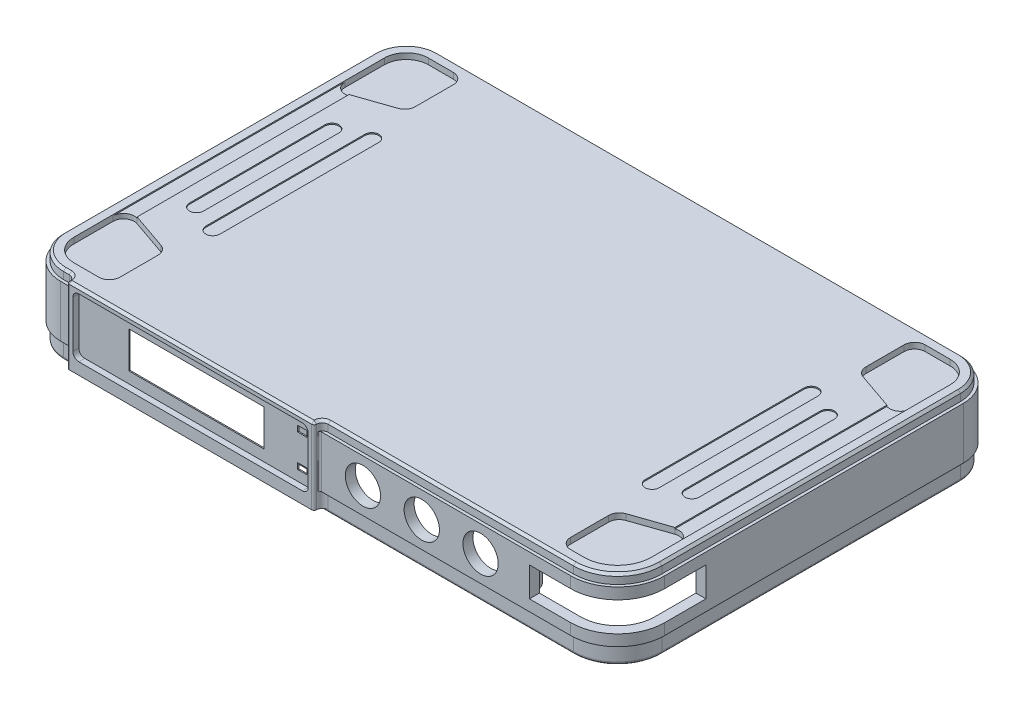
SolidWorks part; units mm, degrees
ref_plane "Front Plane" through (0, 0, 0) normal (0, 0, 1) x (1, 0, 0)
ref_plane "Top Plane" through (0, 0, 0) normal (0, 1, 0) x (1, 0, 0)
ref_plane "Right Plane" through (0, 0, 0) normal (1, 0, 0) x (0, 0, -1)
sketch "Sketch1" plane through (0, 0, 0) normal (0, 1, 0) x (1, 0, 0)
  line L0 (-50.35, 0) -> (50.35, 0) construction
  line L1 (0, 32.39) -> (0, -32.39) construction
  line L8 (44.35, 32.39) -> (-44.35, 32.39)
  line L9 (-50.35, 26.39) -> (-50.35, -26.39)
  line L10 (-44.35, -32.39) -> (42.35, -32.39)
  line L11 (50.35, -24.39) -> (50.35, 26.39)
  arc A2 (42.35, -32.39) -> (50.35, -24.39) centre (42.35, -24.39) ccw
  arc A8 (50.35, 26.39) -> (44.35, 32.39) centre (44.35, 26.39) ccw
  arc A9 (-44.35, 32.39) -> (-50.35, 26.39) centre (-44.35, 26.39) ccw
  arc A10 (-50.35, -26.39) -> (-44.35, -32.39) centre (-44.35, -26.39) ccw
  dimension "D2" = 64.78
  dimension "D3" = 6
  dimension "D1" = 100.7
  dimension "D4" = 0
  dimension "D5" = 8
extrude "Boss-Extrude1" add sketch "Sketch1" along normal blind 13
sketch "Sketch3" plane through (0, 13, 0) normal (0, 1, 0) x (1, 0, 0)
  line L0 (-50.35, 0) -> (50.35, 0) construction
  line L1 (-50.35, 26.39) -> (-50.35, -26.39) construction
  line L2 (42.35, -30.1389) -> (40.0989, -30.1389)
  line L3 (0, -32.39) -> (0, 32.39) construction
  line L4 (-44.35, -32.39) -> (42.35, -32.39) construction
  line L5 (50.35, -24.39) -> (50.35, 26.39) construction
  line L6 (-45.9859, -18.557) -> (-39.9859, -20.6263) construction
  line L8 (-48.0989, -19.7157) -> (-48.0989, -26.39)
  line L9 (-39.5121, -20.1524) -> (-45.7121, -18.014)
  line L10 (-38.2989, -28.3389) -> (-38.2989, -21.854)
  line L11 (-44.35, -30.1389) -> (-40.0989, -30.1389)
  line L13 (44.35, 32.39) -> (-44.35, 32.39) construction
  line L14 (-44.35, 30.1389) -> (-40.0989, 30.1389)
  line L15 (-38.2989, 28.3389) -> (-38.2989, 21.854)
  line L16 (-39.5121, 20.1524) -> (-45.7121, 18.014)
  line L17 (-48.0989, 19.7157) -> (-48.0989, 26.39)
  line L18 (48.0989, 19.7157) -> (48.0989, 26.39)
  line L19 (39.5121, 20.1524) -> (45.7121, 18.014)
  line L20 (38.2989, 28.3389) -> (38.2989, 21.854)
  line L21 (44.35, 30.1389) -> (40.0989, 30.1389)
  line L23 (38.2989, -28.3389) -> (38.2989, -21.854)
  line L24 (39.5121, -20.1524) -> (45.7121, -18.014)
  line L25 (48.0989, -19.7157) -> (48.0989, -24.39)
  arc A0 (-40.0989, 30.1389) -> (-38.2989, 28.3389) centre (-40.0989, 28.3389) cw
  arc A1 (-38.2989, 21.854) -> (-39.5121, 20.1524) centre (-40.0989, 21.854) cw
  arc A2 (-45.7121, 18.014) -> (-48.0989, 19.7157) centre (-46.2989, 19.7157) cw
  arc A3 (-48.0989, 26.39) -> (-44.35, 30.1389) centre (-44.35, 26.39) cw
  arc A4 (-50.35, -26.39) -> (-44.35, -32.39) centre (-44.35, -26.39) ccw construction
  arc A5 (42.35, -32.39) -> (50.35, -24.39) centre (42.35, -24.39) ccw construction
  arc A6 (38.2989, -28.3389) -> (40.0989, -30.1389) centre (40.0989, -28.3389) ccw
  arc A8 (-48.0989, -26.39) -> (-44.35, -30.1389) centre (-44.35, -26.39) ccw
  arc A9 (-45.7121, -18.014) -> (-48.0989, -19.7157) centre (-46.2989, -19.7157) ccw
  arc A10 (-38.2989, -21.854) -> (-39.5121, -20.1524) centre (-40.0989, -21.854) ccw
  arc A11 (-40.0989, -30.1389) -> (-38.2989, -28.3389) centre (-40.0989, -28.3389) ccw
  arc A13 (38.2989, -21.854) -> (39.5121, -20.1524) centre (40.0989, -21.854) cw
  arc A14 (45.7121, -18.014) -> (48.0989, -19.7157) centre (46.2989, -19.7157) cw
  arc A15 (48.0989, -24.39) -> (42.35, -30.1389) centre (42.35, -24.39) cw
  arc A16 (48.0989, 26.39) -> (44.35, 30.1389) centre (44.35, 26.39) ccw
  arc A17 (45.7121, 18.014) -> (48.0989, 19.7157) centre (46.2989, 19.7157) ccw
  arc A18 (38.2989, 21.854) -> (39.5121, 20.1524) centre (40.0989, 21.854) ccw
  arc A19 (40.0989, 30.1389) -> (38.2989, 28.3389) centre (40.0989, 28.3389) ccw
  point P64 (-38.8262, -29.6117)
  point P65 (-47.3438, -18.25)
  point P66 (-38.6333, -20.8091)
  point P67 (-47.0009, -29.0409)
  point P68 (-38.6333, 20.8091)
  point P75 (-47.3438, 18.25)
  dimension "D3" = 36.5
  dimension "D1" = 1.8
  dimension "D6" = 0
  dimension "D7" = 0
  dimension "D2" = 9.8
  dimension "D5" = 14.2
  dimension "D9" = 4.2511
extrude "Cut-Extrude1" cut sketch "Sketch3" against normal blind 1 contours L11 A11 L10 A10 L9 A9 L8 A8 | A15 L25 A14 L24 A13 L23 A6 L2 | L21 A19 L20 A18 L19 A17 L18 A16 | A3 L17 A2 L16 A1 L15 A0 L14
sketch "Sketch4" plane through (0, 13, 0) normal (0, 1, 0) x (1, 0, 0)
  line L0 (-48.0989, 19.7157) -> (-48.0989, -19.7157)
  line L1 (-45.7121, 0) -> (-48.0989, 0) construction
  line L2 (-40.9252, 0) -> (-43.3121, 0) construction
  line L3 (-42.1186, 11.5066) -> (-42.1186, -11.5066) construction
  line L4 (-40.9252, 11.5066) -> (-40.9252, -11.5066)
  line L5 (-45.7121, 18.014) -> (-45.7121, -18.014)
  line L6 (-43.3121, 11.5066) -> (-43.3121, -11.5066)
  line L7 (-37.3317, 13.5066) -> (-37.3317, -13.5066) construction
  line L8 (-36.1383, 13.5066) -> (-36.1383, -13.5066)
  line L9 (-38.5252, 13.5066) -> (-38.5252, -13.5066)
  line L10 (-36.1383, 0) -> (-38.5252, 0) construction
  line L11 (-45.7121, 0) -> (-43.3121, 0) construction
  line L12 (-40.9252, 0) -> (-38.5252, 0) construction
  line L13 (0, 32.39) -> (0, -32.39) construction
  line L14 (44.35, 32.39) -> (-44.35, 32.39) construction
  line L16 (42.1186, 11.5066) -> (42.1186, -11.5066) construction
  line L17 (40.9252, 11.5066) -> (40.9252, -11.5066)
  line L18 (43.3121, 11.5066) -> (43.3121, -11.5066)
  line L19 (37.3317, 13.5066) -> (37.3317, -13.5066) construction
  line L20 (36.1383, 13.5066) -> (36.1383, -13.5066)
  line L21 (38.5252, 13.5066) -> (38.5252, -13.5066)
  line L22 (40.9252, 0) -> (38.5252, 0) construction
  line L23 (45.7121, 0) -> (43.3121, 0) construction
  line L24 (36.1383, 0) -> (38.5252, 0) construction
  line L25 (40.9252, 0) -> (43.3121, 0) construction
  line L26 (45.7121, 0) -> (48.0989, 0) construction
  line L27 (45.7121, 18.014) -> (45.7121, -18.014)
  line L28 (48.0989, 19.7157) -> (48.0989, -19.7157)
  arc A0 (-48.0989, 19.7157) -> (-45.7121, 18.014) centre (-46.2989, 19.7157) ccw construction
  arc A1 (-45.7121, -18.014) -> (-48.0989, -19.7157) centre (-46.2989, -19.7157) ccw construction
  arc A2 (-48.0989, 19.7157) -> (-45.7121, 18.014) centre (-46.2989, 19.7157) ccw
  arc A3 (-45.7121, -18.014) -> (-48.0989, -19.7157) centre (-46.2989, -19.7157) ccw
  arc A4 (-40.9252, 11.5066) -> (-43.3121, 11.5066) centre (-42.1186, 11.5066) ccw
  arc A5 (-43.3121, -11.5066) -> (-40.9252, -11.5066) centre (-42.1186, -11.5066) ccw
  arc A6 (-36.1383, 13.5066) -> (-38.5252, 13.5066) centre (-37.3317, 13.5066) ccw
  arc A7 (-38.5252, -13.5066) -> (-36.1383, -13.5066) centre (-37.3317, -13.5066) ccw
  arc A8 (40.9252, 11.5066) -> (43.3121, 11.5066) centre (42.1186, 11.5066) cw
  arc A9 (43.3121, -11.5066) -> (40.9252, -11.5066) centre (42.1186, -11.5066) cw
  arc A10 (36.1383, 13.5066) -> (38.5252, 13.5066) centre (37.3317, 13.5066) cw
  arc A11 (38.5252, -13.5066) -> (36.1383, -13.5066) centre (37.3317, -13.5066) cw
  arc A12 (45.7121, -18.014) -> (48.0989, -19.7157) centre (46.2989, -19.7157) cw
  arc A13 (48.0989, 19.7157) -> (45.7121, 18.014) centre (46.2989, 19.7157) cw
  point P4 (-42.1186, 0)
  point P10 (-42.1186, 12.7)
  point P11 (-42.1186, -12.7)
  point P17 (-37.3317, 0)
  point P28 (-37.3317, -14.7)
  point P29 (-37.3317, 14.7)
  point P38 (42.1186, 0)
  point P45 (37.3317, 0)
  point P62 (37.3317, 14.7)
  point P63 (37.3317, -14.7)
  point P64 (42.1186, -12.7)
  point P65 (42.1186, 12.7)
  dimension "D1" = 8.0188
  dimension "D2" = 2.4
  dimension "D3" = 25.4
  dimension "D4" = 29.4
extrude "Cut-Extrude2" cut sketch "Sketch4" against normal blind 0.2
sketch "Sketch5" plane through (0, 13, 0) normal (0, 1, 0) x (1, 0, 0)
  line L0 (44.35, 31.89) -> (-44.35, 31.89)
  line L1 (-49.85, 26.39) -> (-49.85, -26.39)
  line L2 (-44.35, -31.89) -> (42.35, -31.89)
  line L3 (49.85, -24.39) -> (49.85, 26.39)
  line L4 (44.35, 32.39) -> (-44.35, 32.39)
  line L5 (-50.35, 26.39) -> (-50.35, -26.39)
  line L6 (-44.35, -32.39) -> (42.35, -32.39)
  line L7 (50.35, -24.39) -> (50.35, 26.39)
  line L8 (44.35, 32.39) -> (-44.35, 32.39)
  line L9 (-50.35, 26.39) -> (-50.35, -26.39)
  line L10 (-44.35, -32.39) -> (42.35, -32.39)
  line L11 (50.35, -24.39) -> (50.35, 26.39)
  arc A0 (-44.35, 31.89) -> (-49.85, 26.39) centre (-44.35, 26.39) ccw
  arc A1 (-49.85, -26.39) -> (-44.35, -31.89) centre (-44.35, -26.39) ccw
  arc A2 (42.35, -31.89) -> (49.85, -24.39) centre (42.35, -24.39) ccw
  arc A3 (49.85, 26.39) -> (44.35, 31.89) centre (44.35, 26.39) ccw
  arc A4 (50.35, 26.39) -> (44.35, 32.39) centre (44.35, 26.39) ccw
  arc A5 (-44.35, 32.39) -> (-50.35, 26.39) centre (-44.35, 26.39) ccw
  arc A6 (-50.35, -26.39) -> (-44.35, -32.39) centre (-44.35, -26.39) ccw
  arc A7 (42.35, -32.39) -> (50.35, -24.39) centre (42.35, -24.39) ccw
  arc A8 (50.35, 26.39) -> (44.35, 32.39) centre (44.35, 26.39) ccw
  arc A9 (-44.35, 32.39) -> (-50.35, 26.39) centre (-44.35, 26.39) ccw
  arc A10 (-50.35, -26.39) -> (-44.35, -32.39) centre (-44.35, -26.39) ccw
  arc A11 (42.35, -32.39) -> (50.35, -24.39) centre (42.35, -24.39) ccw
  dimension "D2" = 0.5
  dimension "D1" = 0
extrude "Cut-Extrude3" cut sketch "Sketch5" against normal blind 1.6
sketch "Sketch6" plane through (0, 0, 0) normal (0, -1, 0) x (1, 0, 0)
  line L4 (-44.35, -32.39) -> (44.35, -32.39)
  line L5 (-50.35, 26.39) -> (-50.35, -26.39)
  line L6 (42.35, 32.39) -> (-44.35, 32.39)
  line L7 (50.35, -26.39) -> (50.35, 24.39)
  line L8 (-44.35, -32.39) -> (44.35, -32.39)
  line L9 (-50.35, 26.39) -> (-50.35, -26.39)
  line L10 (42.35, 32.39) -> (-44.35, 32.39)
  line L11 (50.35, -26.39) -> (50.35, 24.39)
  line L12 (49.85, -26.39) -> (49.85, 24.39)
  line L13 (-44.35, -31.89) -> (44.35, -31.89)
  line L14 (-49.85, 26.39) -> (-49.85, -26.39)
  line L15 (42.35, 31.89) -> (-44.35, 31.89)
  line L16 (49.85, -26.39) -> (49.85, 24.39)
  line L17 (-44.35, -31.89) -> (44.35, -31.89)
  line L18 (-49.85, 26.39) -> (-49.85, -26.39)
  line L19 (42.35, 31.89) -> (-44.35, 31.89)
  arc A4 (44.35, -32.39) -> (50.35, -26.39) centre (44.35, -26.39) ccw
  arc A5 (-50.35, -26.39) -> (-44.35, -32.39) centre (-44.35, -26.39) ccw
  arc A6 (-44.35, 32.39) -> (-50.35, 26.39) centre (-44.35, 26.39) ccw
  arc A7 (50.35, 24.39) -> (42.35, 32.39) centre (42.35, 24.39) ccw
  arc A8 (44.35, -32.39) -> (50.35, -26.39) centre (44.35, -26.39) ccw
  arc A9 (-50.35, -26.39) -> (-44.35, -32.39) centre (-44.35, -26.39) ccw
  arc A10 (-44.35, 32.39) -> (-50.35, 26.39) centre (-44.35, 26.39) ccw
  arc A11 (50.35, 24.39) -> (42.35, 32.39) centre (42.35, 24.39) ccw
  arc A12 (44.35, -31.89) -> (49.85, -26.39) centre (44.35, -26.39) ccw
  arc A13 (-49.85, -26.39) -> (-44.35, -31.89) centre (-44.35, -26.39) ccw
  arc A14 (-44.35, 31.89) -> (-49.85, 26.39) centre (-44.35, 26.39) ccw
  arc A15 (49.85, 24.39) -> (42.35, 31.89) centre (42.35, 24.39) ccw
  arc A16 (44.35, -31.89) -> (49.85, -26.39) centre (44.35, -26.39) ccw
  arc A17 (-49.85, -26.39) -> (-44.35, -31.89) centre (-44.35, -26.39) ccw
  arc A18 (-44.35, 31.89) -> (-49.85, 26.39) centre (-44.35, 26.39) ccw
  arc A19 (49.85, 24.39) -> (42.35, 31.89) centre (42.35, 24.39) ccw
  dimension "D1" = 0
  dimension "D2" = 0
extrude "Cut-Extrude4" cut sketch "Sketch6" against normal blind 2.6
sketch "Sketch7" plane through (0, 0, 31.89) normal (0, 0, 1) x (1, 0, 0)
  line L0 (-44.35, 13) -> (42.35, 13) construction
  line L1 (-42.35, 13) -> (-0.35, 13)
  line L2 (-42.35, 13) -> (-42.35, 0)
  line L3 (-42.35, 0) -> (-0.35, 0)
  line L4 (-0.35, 13) -> (-0.35, 0)
  line L5 (-42.35, 13) -> (-0.35, 0) construction
  line L6 (-42.35, 0) -> (-0.35, 13) construction
  line L7 (42.35, 0) -> (-44.35, 0) construction
  line L8 (-50.35, 11.4) -> (-50.35, 2.6) construction
  point P0 (-21.35, 6.5)
  dimension "D1" = 42
  dimension "D2" = 8
extrude "Boss-Extrude2" add sketch "Sketch7" along normal blind 1.4
sketch "Sketch8" plane through (-49.85, 0, 0) normal (-1, 0, 0) x (0, 0, 1)
  line L0 (0, 0) -> (0, 13) construction
  line L1 (26.39, 0) -> (-26.39, 0) construction
  line L2 (-26.39, 13) -> (26.39, 13) construction
  line L3 (-32.39, 11.4) -> (-32.39, 2.6) construction
  line L4 (-13.39, 11.4) -> (-13.39, 2.6) construction
  line L5 (-26.39, 11.4) -> (26.39, 11.4) construction
  line L6 (26.39, 2.6) -> (-26.39, 2.6) construction
  circle A0 centre (-13.39, 7) radius 6
  circle A1 centre (13.39, 7) radius 6
  point P8 (-19.39, 7)
  point P13 (-7.39, 6.5)
  point P16 (7.39, 6.5)
  point P17 (19.39, 7)
  line M5 (-26.39, 11.4) -> (26.39, 11.4)
  dimension "D1" = 12
  dimension "D2" = 13
extrude "Cut-Extrude6" cut sketch "Sketch8" along normal up to surface (0.5 mm away) contours A0 M5 | A1 M5 up to face at (-50.35, 7, 0)
sketch "Sketch9" plane through (0, 0, 33.29) normal (0, 0, 1) x (1, 0, 0)
  line L0 (-42.35, 0) -> (-0.35, 0) construction
  line L1 (-40.35, 12) -> (-2.35, 12)
  line L2 (-41.35, 11) -> (-41.35, 3)
  line L3 (-40.35, 2) -> (-2.35, 2)
  line L4 (-1.35, 11) -> (-1.35, 3)
  line L5 (-41.35, 12) -> (-1.35, 2) construction
  line L6 (-41.35, 2) -> (-1.35, 12) construction
  line L7 (-42.35, 7) -> (-0.35, 7) construction
  line L8 (-42.35, 11.4) -> (-42.35, 2.6) construction
  line L9 (-0.35, 2.6) -> (-0.35, 11.4) construction
  line L10 (-21.35, 13) -> (-21.35, 0) construction
  line L11 (-0.35, 13) -> (-42.35, 13) construction
  arc A0 (-40.35, 12) -> (-41.35, 11) centre (-40.35, 11) ccw
  arc A1 (-41.35, 3) -> (-40.35, 2) centre (-40.35, 3) ccw
  arc A2 (-1.35, 3) -> (-2.35, 2) centre (-2.35, 3) cw
  arc A3 (-2.35, 12) -> (-1.35, 11) centre (-2.35, 11) cw
  point P0 (-21.35, 7)
  dimension "D4" = 1
  dimension "D1" = 2
  dimension "D2" = 10
  dimension "D3" = 40
extrude "Cut-Extrude7" cut sketch "Sketch9" against normal blind 1
sketch "Sketch10" plane through (0, 0, -31.89) normal (0, 0, -1) x (-1, 0, 0)
  line L0 (-23.85, 6.5) -> (-34.85, 6.5) construction
  line L1 (-23.85, 0) -> (-34.85, 0)
  line L2 (-23.85, 13) -> (-34.85, 13)
  line L3 (-29.35, 11.4) -> (-29.35, 2.6) construction
  line L4 (-44.35, 11.4) -> (44.35, 11.4) construction
  line L5 (-50.35, 11.4) -> (-50.35, 2.6) construction
  line L6 (44.35, 2.6) -> (-44.35, 2.6) construction
  line L7 (44.35, 0) -> (-44.35, 0) construction
  line L9 (50.35, 11.4) -> (50.35, 2.6) construction
  line L10 (-44.35, 13) -> (44.35, 13) construction
  arc A0 (-23.85, 0) -> (-23.85, 13) centre (-23.85, 6.5) ccw
  arc A1 (-34.85, 13) -> (-34.85, 0) centre (-34.85, 6.5) ccw
  circle A2 centre (33.85, 6.5) radius 6.5
  circle A3 centre (-34.85, 6.5) radius 5 construction
  point P2 (-29.35, 6.5)
  point P7 (-17.35, 6.5)
  point P14 (-41.35, 6.5)
  point P23 (-34.85, 11.5)
  point P24 (40.35, 6.5)
  dimension "D2" = 24
  dimension "D3" = 11
  dimension "D5" = 1.5
  dimension "D6" = 10
  dimension "D1" = 9
  dimension "D4" = 10
extrude "Cut-Extrude8" cut sketch "Sketch10" along normal up to surface (0.5 mm away) up to face at (0, 7, -32.39)
fillet "Fillet1" radius 0.4 4 edges at (-42.35, 7, 32.39) (-42.35, 6.5, 33.29) (-0.35, 7, 32.39) (-0.35, 6.5, 33.29)
fillet "Fillet2" radius 1 2 edges at (-0.35, 12.2, 31.89) (-42.35, 12.2, 31.89)
chamfer "Chamfer1" distance 0.4 angle 45 14 edges at (0, 13, -31.89) (48.2391, 13, -30.2791) (-48.2391, 13, -30.2791) (49.85, 13, -1) (-49.85, 13, 0) (47.6533, 13, 29.6933) (-48.2391, 13, 30.2791) (21.5, 13, 31.89) (-43.85, 13, 31.89) (-0.0571, 13, 32.1829) (-42.6429, 13, 32.1829) (-0.4672, 13, 33.1728) (-42.2328, 13, 33.1728) (-21.35, 13, 33.29)
sketch "Sketch11" plane through (0, 0, 0) normal (0, -1, 0) x (1, 0, 0)
  line L0 (-43.35, 30.69) -> (-44.35, 30.69)
  line L1 (-48.65, 26.39) -> (-48.65, -26.39)
  line L2 (-44.35, -30.69) -> (44.35, -30.69)
  line L3 (48.65, -26.39) -> (48.65, 24.39)
  line L4 (42.35, 30.69) -> (0.65, 30.69)
  line L5 (-1.3994, 32.09) -> (-41.3006, 32.09)
  line L6 (-0.75, 33.29) -> (-41.95, 33.29)
  line L7 (-0.75, 33.29) -> (-41.95, 33.29)
  line L8 (-43.35, 31.89) -> (-44.35, 31.89)
  line L9 (-43.35, 31.89) -> (-44.35, 31.89)
  line L10 (-49.85, 26.39) -> (-49.85, -26.39)
  line L11 (-49.85, 26.39) -> (-49.85, -26.39)
  line L24 (-44.35, -31.89) -> (44.35, -31.89)
  line L25 (-44.35, -31.89) -> (44.35, -31.89)
  line L26 (49.85, -26.39) -> (49.85, 24.39)
  line L27 (49.85, -26.39) -> (49.85, 24.39)
  line L28 (42.35, 31.89) -> (0.65, 31.89)
  line L29 (42.35, 31.89) -> (0.65, 31.89)
  arc A0 (-44.35, 30.69) -> (-48.65, 26.39) centre (-44.35, 26.39) ccw
  arc A1 (-48.65, -26.39) -> (-44.35, -30.69) centre (-44.35, -26.39) ccw
  arc A2 (44.35, -30.69) -> (48.65, -26.39) centre (44.35, -26.39) ccw
  arc A3 (48.65, 24.39) -> (42.35, 30.69) centre (42.35, 24.39) ccw
  arc A4 (-1.3994, 32.09) -> (0.65, 30.69) centre (0.65, 32.89) ccw
  arc A5 (-43.35, 30.69) -> (-41.3006, 32.09) centre (-43.35, 32.89) ccw
  arc A6 (-41.95, 33.29) -> (-42.35, 32.89) centre (-41.95, 32.89) ccw
  arc A7 (-41.95, 33.29) -> (-42.35, 32.89) centre (-41.95, 32.89) ccw
  arc A8 (-43.35, 31.89) -> (-42.35, 32.89) centre (-43.35, 32.89) ccw
  arc A9 (-43.35, 31.89) -> (-42.35, 32.89) centre (-43.35, 32.89) ccw
  arc A10 (-44.35, 31.89) -> (-49.85, 26.39) centre (-44.35, 26.39) ccw
  arc A11 (-44.35, 31.89) -> (-49.85, 26.39) centre (-44.35, 26.39) ccw
  arc A26 (-49.85, -26.39) -> (-44.35, -31.89) centre (-44.35, -26.39) ccw
  arc A27 (-49.85, -26.39) -> (-44.35, -31.89) centre (-44.35, -26.39) ccw
  arc A28 (44.35, -31.89) -> (49.85, -26.39) centre (44.35, -26.39) ccw
  arc A29 (44.35, -31.89) -> (49.85, -26.39) centre (44.35, -26.39) ccw
  arc A30 (49.85, 24.39) -> (42.35, 31.89) centre (42.35, 24.39) ccw
  arc A31 (49.85, 24.39) -> (42.35, 31.89) centre (42.35, 24.39) ccw
  arc A32 (-0.35, 32.89) -> (0.65, 31.89) centre (0.65, 32.89) ccw
  arc A33 (-0.35, 32.89) -> (0.65, 31.89) centre (0.65, 32.89) ccw
  arc A34 (-0.35, 32.89) -> (-0.75, 33.29) centre (-0.75, 32.89) ccw
  arc A35 (-0.35, 32.89) -> (-0.75, 33.29) centre (-0.75, 32.89) ccw
  dimension "D1" = 0
extrude "Cut-Extrude9" cut sketch "Sketch11" against normal blind 11.5 contours A5 L0 A0 L1 A1 L2 A2 L3 A3 L4 A4 L5
sketch "Sketch12" plane through (0, 0, 32.29) normal (0, 0, 1) x (1, 0, 0)
  line L0 (-41.35, 7) -> (-1.35, 7) construction
  line L1 (-32.85, 10.1) -> (-9.85, 10.1)
  line L2 (-32.85, 10.1) -> (-32.85, 3.9)
  line L3 (-32.85, 3.9) -> (-9.85, 3.9)
  line L4 (-9.85, 10.1) -> (-9.85, 3.9)
  line L5 (-32.85, 10.1) -> (-9.85, 3.9) construction
  line L6 (-32.85, 3.9) -> (-9.85, 10.1) construction
  line L7 (-41.35, 11) -> (-41.35, 3) construction
  line L8 (-1.35, 3) -> (-1.35, 11) construction
  line L9 (-21.35, 12) -> (-21.35, 2) construction
  line L10 (-2.35, 12) -> (-40.35, 12) construction
  line L11 (-40.35, 2) -> (-2.35, 2) construction
  line L13 (-4.15, 10.25) -> (-2.55, 10.25)
  line L14 (-4.15, 10.25) -> (-4.15, 9.25)
  line L15 (-4.15, 9.25) -> (-2.55, 9.25)
  line L16 (-2.55, 10.25) -> (-2.55, 9.25)
  line L17 (-4.15, 10.25) -> (-2.55, 9.25) construction
  line L18 (-4.15, 9.25) -> (-2.55, 10.25) construction
  line L19 (-4.15, 4.75) -> (-2.55, 4.75)
  line L20 (-4.15, 4.75) -> (-4.15, 3.75)
  line L21 (-4.15, 3.75) -> (-2.55, 3.75)
  line L22 (-2.55, 4.75) -> (-2.55, 3.75)
  line L23 (-4.15, 4.75) -> (-2.55, 3.75) construction
  line L24 (-4.15, 3.75) -> (-2.55, 4.75) construction
  line L25 (-2.55, 10.25) -> (-2.55, 12) construction
  line L26 (-2.35, 12) -> (-40.35, 12) construction
  line L27 (-2.55, 3.75) -> (-2.55, 2) construction
  line L28 (-40.35, 2) -> (-2.35, 2) construction
  line L29 (-1.35, 3) -> (-1.35, 11) construction
  point P0 (-21.35, 7)
  point P17 (-3.35, 9.75)
  point P22 (-3.35, 4.25)
  dimension "D1" = 6.2
  dimension "D2" = 23
  dimension "D3" = 1
  dimension "D4" = 1.6
  dimension "D5" = 1.2
  dimension "D6" = 4.5
  dimension "D7" = 1.75
extrude "Cut-Extrude10" cut sketch "Sketch12" against normal blind 12
sketch "Sketch13" plane through (-49.85, 0, 0) normal (-1, 0, 0) x (0, 0, 1)
  circle A0 centre (-13.39, 7) radius 4.5
  circle A1 centre (13.39, 7) radius 4.5
  dimension "D1" = 9
extrude "Cut-Extrude11" cut sketch "Sketch13" against normal blind 12
sketch "Sketch14" plane through (0, 0, -31.89) normal (0, 0, -1) x (-1, 0, 0)
  line L0 (-34.85, 6.5) -> (-21.7583, 6.5) construction
  line L1 (-30.967, 9.65) -> (-21.7583, 9.65)
  line L2 (-30.967, 3.35) -> (-21.7583, 3.35)
  circle A0 centre (33.85, 6.5) radius 2.25
  arc A2 (-21.7583, 3.35) -> (-21.7583, 9.65) centre (-21.7583, 6.5) ccw
  arc A3 (-30.967, 9.65) -> (-30.967, 3.35) centre (-34.85, 6.5) ccw
  arc A4 (-39.1208, 11.4) -> (-40.05, 2.6) centre (-34.85, 6.5) ccw construction
  arc A5 (-18.65, 2.6) -> (-19.5792, 11.4) centre (-23.85, 6.5) ccw construction
  point P13 (-17.3859, 7.1825)
  point P24 (-18.6083, 6.5)
  dimension "D1" = 4.4083
  dimension "D3" = 10
  dimension "D5" = 4.5
  dimension "D2" = 6.3
  dimension "D4" = 1.4
extrude "Cut-Extrude12" cut sketch "Sketch14" against normal blind 12
sketch "Sketch15" plane through (0, 0, 32.39) normal (0, 0, 1) x (1, 0, 0)
  line L0 (27.05, 7) -> (17.05, 7) construction
  line L1 (7.05, 7) -> (17.05, 7) construction
  line L2 (12.05, 11.4) -> (12.05, 2.6) construction
  line L3 (0.05, 11.4) -> (0.05, 2.6) construction
  line L4 (50.35, 11.4) -> (50.35, 2.6) construction
  line L5 (0.05, 11.4) -> (42.35, 11.4) construction
  line L6 (42.35, 2.6) -> (0.65, 2.6) construction
  line L7 (35.35, 9.5) -> (50.35, 9.5)
  line L8 (35.35, 9.5) -> (35.35, 4.5)
  line L9 (35.35, 4.5) -> (50.35, 4.5)
  line L10 (50.35, 9.5) -> (50.35, 4.5)
  line L11 (35.35, 9.5) -> (50.35, 4.5) construction
  line L12 (35.35, 4.5) -> (50.35, 9.5) construction
  circle A0 centre (7.05, 7) radius 3
  circle A1 centre (17.05, 7) radius 3
  circle A2 centre (27.05, 7) radius 3
  point P12 (20.05, 7)
  point P13 (12.05, 7)
  point P14 (4.05, 7)
  point P17 (42.85, 7)
  dimension "D1" = 6
  dimension "D2" = 16
  dimension "D3" = 10
  dimension "D4" = 4
  dimension "D5" = 15
  dimension "D6" = 5
extrude "Cut-Extrude13" cut sketch "Sketch15" against normal blind 15
sketch "Sketch16" plane through (-48.65, 0, 0) normal (1, 0, 0) x (0, 0, -1)
  line L0 (-26.39, 11.5) -> (-13.39, 11.5) construction
  line L1 (-19.39, 11.5) -> (-15.89, 11.5)
  line L2 (-19.39, 11.5) -> (-19.39, 0)
  line L3 (-19.39, 0) -> (-7.39, 0)
  line L4 (-7.39, 11.5) -> (-7.39, 0)
  line L5 (-26.39, 0) -> (26.39, 0) construction
  line L6 (-13.39, 11.5) -> (13.39, 11.5) construction
  line L11 (-13.39, 0) -> (-13.39, 11.5) construction
  line L12 (-10.89, 11.5) -> (-7.39, 11.5)
  line L13 (-15.89, 11.5) -> (-15.89, 11.4721)
  line L14 (-10.89, 11.5) -> (-10.89, 11.4721)
  line L15 (0, 0) -> (0, 11.5) construction
  line L16 (10.89, 11.5) -> (10.89, 11.4721)
  line L17 (15.89, 11.5) -> (15.89, 11.4721)
  line L18 (10.89, 11.5) -> (7.39, 11.5)
  line L19 (7.39, 11.5) -> (7.39, 0)
  line L20 (19.39, 0) -> (7.39, 0)
  line L21 (19.39, 11.5) -> (19.39, 0)
  line L22 (19.39, 11.5) -> (15.89, 11.5)
  circle A1 centre (-13.39, 7) radius 4.5 construction
  arc A3 (-16.39, 10.3541) -> (-10.39, 10.3541) centre (-13.39, 7) ccw
  arc A4 (-10.89, 11.4721) -> (-10.39, 10.3541) centre (-9.39, 11.4721) ccw
  arc A5 (-15.89, 11.4721) -> (-16.39, 10.3541) centre (-17.39, 11.4721) cw
  arc A6 (15.89, 11.4721) -> (16.39, 10.3541) centre (17.39, 11.4721) ccw
  arc A7 (10.89, 11.4721) -> (10.39, 10.3541) centre (9.39, 11.4721) cw
  arc A8 (16.39, 10.3541) -> (10.39, 10.3541) centre (13.39, 7) cw
  point P5 (-10.89, 10.7417)
  point P17 (-15.89, 10.7417)
  line M6 (26.39, 11.5) -> (13.39, 11.5)
  circle M7 centre (13.39, 7) radius 4.5
  line M8 (13.39, 11.5) -> (-13.39, 11.5)
  circle M9 centre (-13.39, 7) radius 4.5
  line M10 (-13.39, 11.5) -> (-26.39, 11.5)
  line M12 (-26.39, 0) -> (26.39, 0)
  dimension "D2" = 5
  dimension "D4" = 1.5
  dimension "D1" = 12
  dimension "D3" = 5
extrude "Boss-Extrude5" add sketch "Sketch16" along normal blind 2.2 contours A5 L13 L2 L4 L14 A4 M10 M12 M8 M9 | A7 L16 L19 L21 L17 A6 M8 M12 M6 M7
sketch "Sketch18" plane through (0, 11.5, 0) normal (0, -1, 0) x (1, 0, 0)
  line L0 (-48.65, 26.39) -> (-48.65, 24.39) construction
  line L1 (-48.65, 26.39) -> (-48.65, 19.39) construction
  line L4 (-42.35, 30.69) -> (-44.35, 30.69) construction
  line L5 (0, 0) -> (0, 32.39) construction
  line L6 (0, 0) -> (-50.35, 0) construction
  line L7 (-41.85, 31.19) -> (-44.35, 31.19) construction
  line L8 (-49.15, 26.39) -> (-49.15, 23.89) construction
  line L9 (-45, 27.04) -> (-45.5657, 27.6057) construction
  line L10 (-42.35, 31.19) -> (-44.35, 31.19)
  line L11 (-49.15, 26.39) -> (-49.15, 24.39)
  line L14 (-49.15, 23.89) -> (-44.35, 23.89) construction
  line L15 (-41.85, 26.39) -> (-41.85, 31.19) construction
  line L16 (-48.65, 24.39) -> (-44.35, 24.39) construction
  line L17 (-42.35, 26.39) -> (-42.35, 30.69) construction
  line L18 (-42.35, 26.39) -> (-42.35, 31.19)
  line L19 (-44.35, 24.39) -> (-49.15, 24.39)
  line L20 (-6.35, 29.59) -> (-8.35, 29.59) construction
  line L22 (-45, -27.04) -> (-45.5657, -27.6057) construction
  line L23 (-42.35, -30.69) -> (-44.35, -30.69) construction
  line L24 (-48.65, -26.39) -> (-48.65, -24.39) construction
  line L25 (-44.35, -24.39) -> (-49.15, -24.39)
  line L26 (-42.35, -26.39) -> (-42.35, -31.19)
  line L27 (-49.15, -26.39) -> (-49.15, -24.39)
  line L28 (-42.35, -31.19) -> (-44.35, -31.19)
  line L29 (48.65, -26.39) -> (48.65, -24.39) construction
  line L30 (42.35, -30.69) -> (44.35, -30.69) construction
  line L31 (45, -27.04) -> (45.5657, -27.6057) construction
  line L32 (42.35, -31.19) -> (44.35, -31.19)
  line L33 (49.15, -26.39) -> (49.15, -24.39)
  line L34 (42.35, -26.39) -> (42.35, -31.19)
  line L35 (44.35, -24.39) -> (49.15, -24.39)
  line L36 (42.35, 30.69) -> (0.65, 30.69) construction
  line L37 (-8.35, 30.69) -> (0.85, 30.69)
  line L38 (-8.35, 30.69) -> (-8.35, 28.49)
  line L39 (-8.35, 28.49) -> (-6.35, 28.49)
  line L40 (0.85, 30.69) -> (0.85, 28.49)
  line L41 (-50.35, 26.39) -> (-50.35, 17.4692) construction
  line L42 (-6.35, 28.49) -> (-6.35, 29.59)
  line L43 (-6.35, 29.59) -> (-1.15, 29.59)
  line L44 (-1.15, 28.49) -> (-1.15, 29.59)
  line L45 (-1.15, 29.59) -> (0.85, 29.59) construction
  line L46 (-3.75, 29.59) -> (-3.75, 30.69) construction
  line L47 (-1.15, 28.49) -> (0.85, 28.49)
  line L48 (42.35, 32.39) -> (0.05, 32.39) construction
  line L49 (0.85, 28.49) -> (0.85, 27.49) construction
  line L50 (-50.35, 9.3108) -> (-50.35, -9.3108) construction
  line L51 (33.35, 30.69) -> (33.35, 29.49)
  line L52 (42.35, 30.69) -> (0.65, 30.69) construction
  line L53 (30.05, 26.19) -> (28.35, 26.19)
  line L54 (28.35, 26.19) -> (28.35, 27.49)
  line L55 (28.35, 27.49) -> (30.05, 27.49)
  line L56 (32.05, 29.49) -> (32.05, 30.69)
  line L57 (32.05, 30.69) -> (33.35, 30.69)
  line L58 (48.65, -26.39) -> (48.65, 24.39) construction
  line L59 (48.65, 10.99) -> (43.05, 10.99)
  line L60 (48.65, 10.99) -> (48.65, 7.99)
  line L61 (48.65, 7.99) -> (43.05, 7.99)
  line L62 (43.05, 10.99) -> (43.05, 7.99)
  line L63 (50.35, -26.39) -> (50.35, 24.39) construction
  arc A0 (-42.35, 26.39) -> (-44.35, 24.39) centre (-44.35, 26.39) cw
  arc A1 (-44.35, 31.19) -> (-49.15, 26.39) centre (-44.35, 26.39) ccw
  arc A2 (-44.35, 30.69) -> (-48.65, 26.39) centre (-44.35, 26.39) ccw construction
  circle A3 centre (-45, 27.04) radius 0.8
  arc A4 (-44.35, 32.39) -> (-50.35, 26.39) centre (-44.35, 26.39) ccw construction
  arc A5 (-44.35, 30.69) -> (-48.65, 26.39) centre (-44.35, 26.39) ccw construction
  arc A7 (-41.85, 26.39) -> (-44.35, 23.89) centre (-44.35, 26.39) cw construction
  arc A8 (-44.35, -30.69) -> (-48.65, -26.39) centre (-44.35, -26.39) cw construction
  circle A9 centre (-45, -27.04) radius 0.8
  arc A10 (-44.35, -31.19) -> (-49.15, -26.39) centre (-44.35, -26.39) cw
  arc A11 (-42.35, -26.39) -> (-44.35, -24.39) centre (-44.35, -26.39) ccw
  arc A12 (44.35, -30.69) -> (48.65, -26.39) centre (44.35, -26.39) ccw construction
  arc A13 (42.35, -26.39) -> (44.35, -24.39) centre (44.35, -26.39) cw
  arc A14 (44.35, -31.19) -> (49.15, -26.39) centre (44.35, -26.39) ccw
  circle A15 centre (45, -27.04) radius 0.8
  arc A16 (33.35, 29.49) -> (30.05, 26.19) centre (30.05, 29.49) cw
  arc A17 (32.05, 29.49) -> (30.05, 27.49) centre (30.05, 29.49) cw
  point P18 (-48.5926, 30.6326)
  point P20 (-45.5657, 27.6057)
  point P29 (-45, 27.04)
  point P39 (-8.35, 29.59)
  point P59 (-45, -27.04)
  point P60 (-45.5657, -27.6057)
  point P61 (-48.5926, -30.6326)
  point P76 (48.5926, -30.6326)
  point P77 (45.5657, -27.6057)
  point P78 (45, -27.04)
  point P108 (43.05, 9.49)
  dimension "D1" = 42
  dimension "D5" = 1.6
  dimension "D7" = 2
  dimension "D9" = 2.2
  dimension "D11" = 1
  dimension "D13" = 1.3
  dimension "D14" = 1.3
  dimension "D12" = 5
  dimension "D16" = 2
  dimension "D2" = 9.2
  dimension "D3" = 0.9192
  dimension "D4" = 90
  dimension "D6" = 0
  dimension "D8" = 0.5
  dimension "D10" = 2
  dimension "D15" = 31.2
  dimension "D17" = 3
  dimension "D18" = 7.3
  dimension "D19" = 24.4
  dimension "D20" = 54.08
extrude "Boss-Extrude6" add sketch "Sketch18" along normal blind 8.5
fillet "Fillet4" radius 0.8 1 edges at (0.65, 7.25, 30.69)
fillet "Fillet5" radius 2 11 edges at (48.65, 7.25, -24.39) (42.35, 7.25, -30.69) (-42.35, 7.25, -30.69) (-48.65, 7.25, -24.39) (-48.65, 7.25, 24.39) (-42.35, 7.25, 30.9304) (48.65, 7.25, 7.99) (48.65, 7.25, 10.99) (33.35, 7.25, 30.69) (32.05, 7.25, 30.69) (0.85, 7.25, 30.69)
fillet "Fillet6" radius 1 2 edges at (43.05, 7.25, 10.99) (43.05, 7.25, 7.99)
sketch "Sketch19" plane through (0, 3, 0) normal (0, -1, 0) x (1, 0, 0)
  line L0 (45, 9.49) -> (45, 7.99) construction
  line L1 (46.65, 10.99) -> (44.05, 10.99) construction
  line L5 (45, 9.49) -> (45, 10.99) construction
  line L6 (44.05, 7.99) -> (46.65, 7.99) construction
  circle A0 centre (45, 9.49) radius 0.6
  circle A2 centre (45, -27.04) radius 0.8 construction
  circle A3 centre (45, -27.04) radius 0.8 construction
  dimension "D1" = 1.2
  dimension "D2" = 36.53
extrude "Boss-Extrude7" add sketch "Sketch19" along normal blind 1.4
chamfer "Chamfer2" distance 0.4 angle 45 1 edges at (45, 1.6, 8.89)
sketch "Sketch20" plane through (0, 0, 29.59) normal (0, 0, -1) x (-1, 0, 0)
  line L0 (4.15, 4.75) -> (4.15, 3.75) construction
  line L1 (4.15, 3.75) -> (2.55, 3.75) construction
  line L2 (2.55, 3.75) -> (2.55, 4.75) construction
  line L3 (2.55, 4.75) -> (4.15, 4.75) construction
  line L4 (4.15, 10.25) -> (4.15, 9.25) construction
  line L5 (4.15, 9.25) -> (2.55, 9.25) construction
  line L6 (2.55, 9.25) -> (2.55, 10.25) construction
  line L7 (2.55, 10.25) -> (4.15, 10.25) construction
  line L8 (4.15, 4.75) -> (4.15, 3.75)
  line L9 (4.15, 3.75) -> (2.55, 3.75)
  line L10 (2.55, 3.75) -> (2.55, 4.75)
  line L11 (2.55, 4.75) -> (4.15, 4.75)
  line L12 (4.15, 10.25) -> (4.15, 9.25)
  line L13 (4.15, 9.25) -> (2.55, 9.25)
  line L14 (2.55, 9.25) -> (2.55, 10.25)
  line L15 (2.55, 10.25) -> (4.15, 10.25)
extrude "Cut-Extrude14" cut sketch "Sketch20" against normal up to surface (1.1 mm away) up to face at (-5.1766, 7.25, 30.69)
sketch "Sketch21" plane through (0, 0, 0) normal (0, -1, 0) x (1, 0, 0)
  line L0 (0.65, 31.89) -> (0.65, 30.69)
  line L1 (-43.35, 31.89) -> (-43.35, 30.69)
  line L2 (-41.95, 33.29) -> (-0.75, 33.29) construction
  line L3 (-41.95, 33.29) -> (-0.75, 33.29)
  line L4 (-43.35, 30.69) -> (0.65, 30.69)
  arc A0 (-43.35, 31.89) -> (-42.35, 32.89) centre (-43.35, 32.89) ccw construction
  arc A1 (-41.95, 33.29) -> (-42.35, 32.89) centre (-41.95, 32.89) ccw construction
  arc A2 (-0.35, 32.89) -> (-0.75, 33.29) centre (-0.75, 32.89) ccw construction
  arc A3 (-0.35, 32.89) -> (0.65, 31.89) centre (0.65, 32.89) ccw construction
  arc A4 (-43.35, 31.89) -> (-42.35, 32.89) centre (-43.35, 32.89) ccw
  arc A5 (-41.95, 33.29) -> (-42.35, 32.89) centre (-41.95, 32.89) ccw
  arc A6 (-0.35, 32.89) -> (-0.75, 33.29) centre (-0.75, 32.89) ccw
  arc A7 (-0.35, 32.89) -> (0.65, 31.89) centre (0.65, 32.89) ccw
extrude "Boss-Extrude8" add sketch "Sketch21" against normal blind 1
sketch "Sketch22" plane through (0, 0, 0) normal (0, -1, 0) x (1, 0, 0)
  line L1 (42.35, 30.8589) -> (-44.35, 30.8589)
  line L2 (48.8189, 24.39) -> (48.8189, -26.39)
  line L3 (44.35, -30.8589) -> (-44.35, -30.8589)
  line L4 (-48.8189, 26.39) -> (-48.8189, -26.39)
  line L5 (48.8189, 30.8589) -> (-48.8189, -30.8589) construction
  line L6 (-43.35, 31.89) -> (-44.35, 31.89)
  line L7 (-49.85, 26.39) -> (-49.85, -26.39)
  line L8 (-44.35, -31.89) -> (44.35, -31.89)
  line L9 (49.85, -26.39) -> (49.85, 24.39)
  line L10 (42.35, 31.89) -> (0.65, 31.89)
  line L11 (-0.75, 33.29) -> (-41.95, 33.29)
  line L13 (-49.85, 26.39) -> (-49.85, -26.39)
  line L14 (-44.35, -31.89) -> (44.35, -31.89)
  line L15 (49.85, -26.39) -> (49.85, 24.39)
  line L18 (48.8189, -30.8589) -> (-48.8189, 30.8589) construction
  line L19 (49.85, -1) -> (48.8189, -1) construction
  line L20 (49.85, -26.39) -> (49.85, 24.39) construction
  line L21 (42.35, 31.89) -> (-44.35, 31.89)
  arc A0 (-48.8189, -26.39) -> (-44.35, -30.8589) centre (-44.35, -26.39) ccw
  arc A1 (44.35, -30.8589) -> (48.8189, -26.39) centre (44.35, -26.39) ccw
  arc A3 (-44.35, 30.8589) -> (-48.8189, 26.39) centre (-44.35, 26.39) ccw
  arc A4 (42.35, 30.8589) -> (48.8189, 24.39) centre (42.35, 24.39) cw
  arc A5 (48.875, 23.875) -> (41.875, 30.875) centre (41.875, 23.875) ccw construction
  arc A8 (-43.35, 31.89) -> (-42.35, 32.89) centre (-43.35, 32.89) ccw
  arc A9 (-44.35, 31.89) -> (-49.85, 26.39) centre (-44.35, 26.39) ccw
  arc A10 (-49.85, -26.39) -> (-44.35, -31.89) centre (-44.35, -26.39) ccw
  arc A11 (44.35, -31.89) -> (49.85, -26.39) centre (44.35, -26.39) ccw
  arc A12 (49.85, 24.39) -> (42.35, 31.89) centre (42.35, 24.39) ccw
  arc A13 (-0.35, 32.89) -> (0.65, 31.89) centre (0.65, 32.89) ccw
  arc A14 (-0.35, 32.89) -> (-0.75, 33.29) centre (-0.75, 32.89) ccw
  arc A15 (-41.95, 33.29) -> (-42.35, 32.89) centre (-41.95, 32.89) ccw
  arc A17 (-44.35, 31.89) -> (-49.85, 26.39) centre (-44.35, 26.39) ccw
  arc A18 (-49.85, -26.39) -> (-44.35, -31.89) centre (-44.35, -26.39) ccw
  arc A19 (44.35, -31.89) -> (49.85, -26.39) centre (44.35, -26.39) ccw
  arc A20 (49.85, 24.39) -> (42.35, 31.89) centre (42.35, 24.39) ccw
  point P0 (0, 0)
  point P28 (0, 0)
  dimension "D2" = 0
  dimension "D1" = 0
extrude "Boss-Extrude9" add sketch "Sketch22" along normal blind 0.5
fillet "Fillet7" radius 0.5 8 edges at (47.6533, -0.5, 29.6933) (49.85, -0.5, -1) (48.2391, -0.5, -30.2791) (0, -0.5, -31.89) (-48.2391, -0.5, -30.2791) (-49.85, -0.5, 0) (-48.2391, -0.5, 30.2791) (-1, -0.5, 31.89)
